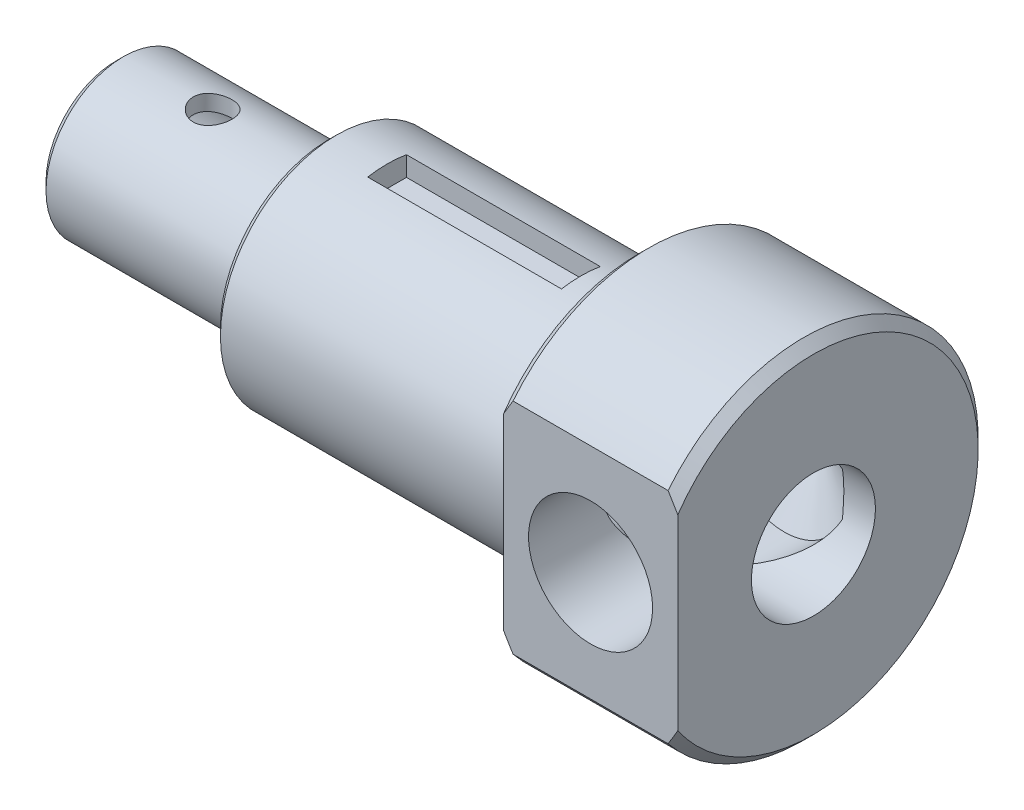
SolidWorks part; units mm, degrees
ref_plane "Спереди" through (0, 0, 0) normal (0, 0, 1) x (1, 0, 0)
ref_plane "Сверху" through (0, 0, 0) normal (0, 1, 0) x (1, 0, 0)
ref_plane "Справа" through (0, 0, 0) normal (1, 0, 0) x (0, 0, -1)
sketch "Эскиз1" plane through (0, 0, 0) normal (0, 0, 1) x (1, 0, 0)
  line L1 (0, 16) -> (0, 20)
  line L2 (0, 20) -> (55, 20)
  line L3 (55, 20) -> (55, 30)
  line L4 (55, 30) -> (135, 30)
  line L5 (135, 30) -> (135, 45)
  line L6 (135, 45) -> (180, 45)
  line L7 (180, 45) -> (180, 16)
  line L9 (0, 0) -> (-45.0163, 0) construction
  line L10 (0, 16) -> (180, 16)
  dimension "D1" = 60
  dimension "D2" = 40
  dimension "D3" = 90
  dimension "D4" = 180
  dimension "D5" = 55
  dimension "D6" = 80
  dimension "D7" = 32
revolve "Повернуть1" add sketch "Эскиз1" angle 360 about L9
sketch "Эскиз15" plane through (180, 0, 0) normal (1, 0, 0) x (0, 0, -1)
  line L0 (-35, 28.2843) -> (-35, -28.2843)
  circle A0 centre (0, 0) radius 45 construction
  circle M2 centre (0, 0) radius 45
  dimension "D1" = 80
extrude "Вырез-Вытянуть9" cut sketch "Эскиз15" against normal through all and the other way through all contours L0 M2
sketch "Эскиз6" plane through (0, 0, 0) normal (0, 0, 1) x (1, 0, 0)
  line L1 (70, 30) -> (120, 30)
  line L2 (70, 30) -> (70, 24.5)
  line L3 (70, 24.5) -> (120, 24.5)
  line L4 (120, 30) -> (120, 24.5)
  line L6 (135, 30) -> (55, 30) construction
  line L7 (55, 30) -> (55, -30) construction
  dimension "D1" = 50
  dimension "D2" = 15
  dimension "D3" = 5.5
extrude "Вырез-Вытянуть4" cut sketch "Эскиз6" against normal mid plane 10
sketch "Эскиз16" plane through (0, 0, 0) normal (0, 1, 0) x (1, 0, 0)
  line L0 (0, 0) -> (55, 0) construction
  line L1 (55, 20) -> (55, -20) construction
  circle A0 centre (25, 0) radius 5
  dimension "D1" = 10
  dimension "D2" = 25
extrude "Вырез-Вытянуть10" cut sketch "Эскиз16" against normal through all both and the other way through all
hole_wizard "Диаметр отверстия Ø0.15 (32)1" positions "Эскиз18" profile "Эскиз19" hole size "Ø0.15" standard "ISO"
sketch "Эскиз18" plane through (0, 0, 35) normal (0, 0, 1) x (1, 0, 0)
  line L0 (135, 0) -> (180, 0) construction
  line L1 (135, 30) -> (135, -30) construction
  line L2 (180, 28.2843) -> (180, -28.2843) construction
  point P0 (157.5, 0)
  point P12 (157.5, 0)
sketch "Эскиз19" plane through (157.5, 0, 35) normal (1, 0, 0) x (0, -1, 0)
  line L0 (0, 0) -> (0, 59.6138)
  line L1 (0, 59.6138) -> (16, 50)
  line L2 (16, 50) -> (16, 0)
  line L5 (16, 0) -> (0, 0)
  line L10 (0, 59.6138) -> (-16, 50) construction
  line L11 (0, -6.35) -> (0, 107.95) construction
  dimension "Диаметр отверстия" = 32
  dimension "Глубина отверстия" = 50
  dimension "Угол заточки сверла" = 118
chamfer "Фаска3" distance 2 angle 45 2 edges at (0, 0, -16) (0, 0, -20)
chamfer "Фаска4" distance 2.5 angle 45 2 edges at (135, 0, -45)
chamfer "Фаска5" distance 2 angle 45 1 edges at (55, 0, -30)
